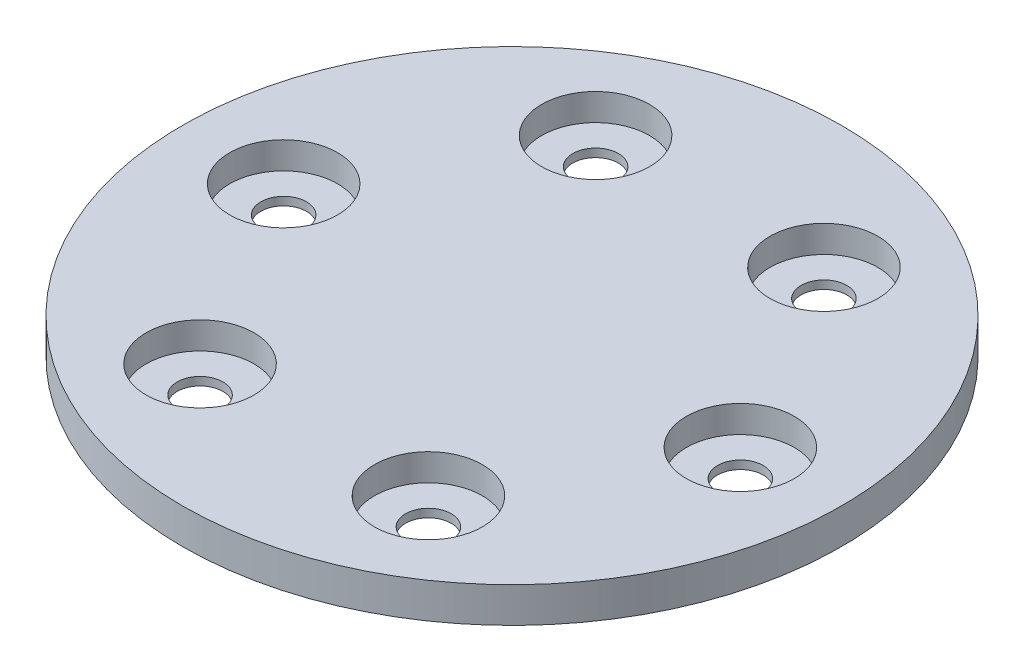
SolidWorks part; units mm, degrees
material "1060 Alloy"
ref_plane "Front Plane" through (0, 0, 0) normal (0, 0, 1) x (1, 0, 0)
ref_plane "Top Plane" through (0, 0, 0) normal (0, 1, 0) x (1, 0, 0)
ref_plane "Right Plane" through (0, 0, 0) normal (1, 0, 0) x (0, 0, -1)
sketch "Sketch1" plane through (0, 0, 0) normal (0, 1, 0) x (1, 0, 0)
  circle A0 centre (0, 0) radius 15.875
  dimension "D1" = 31.75
extrude "Boss-Extrude1" add sketch "Sketch1" along normal blind 1.7
sketch "Sketch7" plane through (0, 1.7, 0) normal (0, 1, 0) x (1, 0, 0)
  circle A0 centre (0, -10.25) radius 0.25
  circle A1 centre (0, 0) radius 9.8
  dimension "D1" = 0.5
  dimension "D2" = 10.25
  dimension "D3" = 19.6
sketch "Sketch8" plane through (0, 1.7, 0) normal (0, 1, 0) x (1, 0, 0)
  line L0 (0, 0) -> (13.2071, 13.2071) construction
  circle A0 centre (7.7782, 7.7782) radius 1
  dimension "D1" = 2
  dimension "D2" = 11
sketch "Sketch9" plane through (0, 1.7, 0) normal (0, 1, 0) x (1, 0, 0)
  circle A0 centre (0, 0) radius 11
  dimension "D1" = 22
hole_wizard "CBORE for M5 Hex Head Bolt1" positions "Sketch13" profile "Sketch14" counterbore size "M5" standard "ISO"
sketch "Sketch13" plane through (0, 1.7, 0) normal (0, 1, 0) x (1, 0, 0)
  circle A0 centre (0, 0) radius 11 construction
  point P0 (-11, 0)
  dimension "D1" = 11
sketch "Sketch14" plane through (-11, 1.7, 0) normal (1, 0, 0) x (0, 0, 1)
  line L0 (0, 0) -> (0, 5.6609)
  line L1 (0, 5.6609) -> (1.1, 5)
  line L2 (1.1, 5) -> (1.1, 1.3)
  line L3 (1.1, 1.3) -> (2.6, 1.3)
  line L4 (2.6, 1.3) -> (2.6, 0)
  line L5 (2.6, 0) -> (0, 0)
  line L10 (0, 5.6609) -> (-1.1, 5) construction
  line L11 (0, -6.35) -> (0, 107.95) construction
  dimension "Hole Dia." = 2.2
  dimension "Hole Depth" = 5
  dimension "C'Bore Dia." = 5.2
  dimension "C'Bore Depth" = 1.3
  dimension "Drill Angle" = 118
pattern_circular "CirPattern1" count 6 over 360 about axis through (0, 1.7, 0) along (0, 1, 0) of "CBORE for M5 Hex Head Bolt1"
